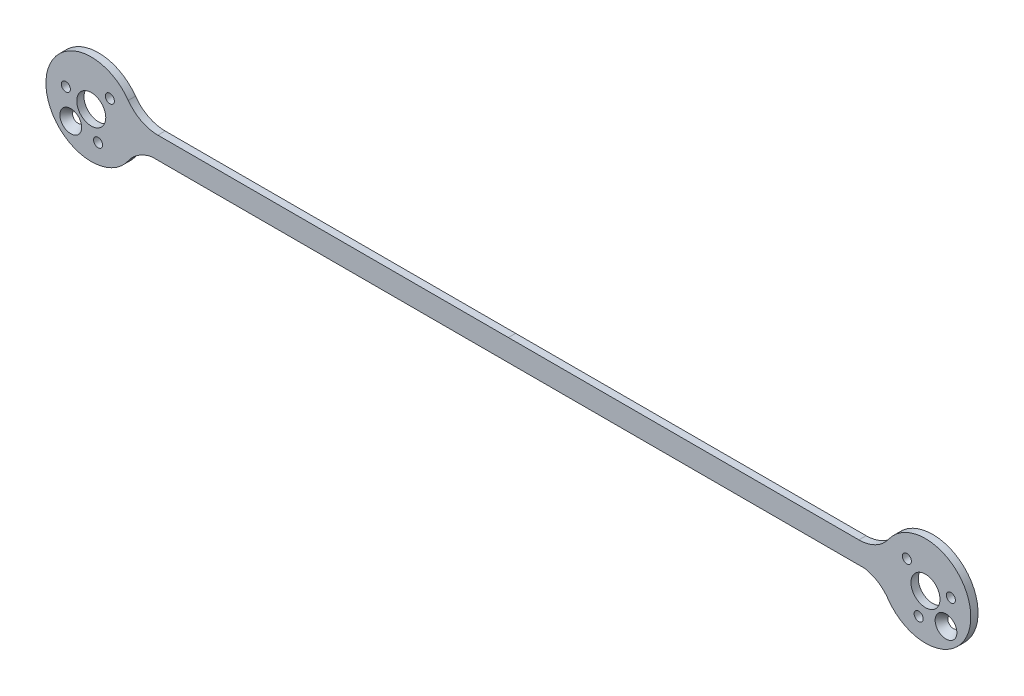
SolidWorks part; units mm, degrees
material "Thornel Mat VMA"
ref_plane "前视基准面" through (0, 0, 0) normal (0, 0, 1) x (1, 0, 0)
ref_plane "上视基准面" through (0, 0, 0) normal (0, 1, 0) x (1, 0, 0)
ref_plane "右视基准面" through (0, 0, 0) normal (1, 0, 0) x (0, 0, -1)
sketch "草图1" plane through (0, 0, 0) normal (0, 0, 1) x (1, 0, 0)
  line L0 (-99.1761, -2.9774) -> (-0.9213, -2.9774)
  line L1 (-0.9213, -2.9774) -> (97.3335, -2.9772)
  line L2 (95.7144, 3.0228) -> (-0.9213, 3.0226)
  line L3 (-0.9213, 3.0226) -> (-97.557, 3.0226)
  circle A0 centre (108.9522, 5.1492) radius 1.25
  arc A1 (-99.1761, -2.9774) -> (-105.6605, -7.1164) centre (-97.4519, -12.8277) ccw
  arc A2 (103.818, -7.1162) -> (97.3335, -2.9772) centre (95.6093, -12.8275) ccw
  arc A3 (103.818, -7.1162) -> (103.8763, 7.2449) centre (114.0786, 0.0228) ccw
  arc A4 (95.7144, 3.0228) -> (103.8763, 7.2449) centre (95.7144, 13.0228) ccw
  arc A5 (-105.7189, 7.2447) -> (-97.557, 3.0226) centre (-97.557, 13.0226) ccw
  arc A6 (-105.7189, 7.2447) -> (-105.6605, -7.1164) centre (-115.9212, 0.0225) ccw
  circle A7 centre (-114.0448, -6.9803) radius 1.25
  circle A8 centre (121.0817, 1.8991) radius 1.25
  circle A9 centre (-122.9242, 1.8991) radius 1.25
  circle A10 centre (-110.7948, 5.1492) radius 1.25
  circle A11 centre (114.0786, 0.0228) radius 4
  circle A12 centre (112.2023, -6.9803) radius 1.25
  circle A13 centre (119.7356, -5.6342) radius 3
  circle A14 centre (119.7356, -5.6342) radius 1.5
  circle A15 centre (-121.5781, -5.6342) radius 1.5
  circle A16 centre (-115.9212, 0.0225) radius 4
  circle A17 centre (-121.5781, -5.6342) radius 3
  dimension "D1" = 6
extrude "凸台-拉伸1" add sketch "草图1" along normal blind 2 contours A5 A6 A1 L0 L1 A2 A3 A4 L2 L3 A17 A16 A13 A12 A11 A10 A9 A8 A7 A0 | A17 A15 | A13 A14 region at (-0.9213, 0.1812, 0) region at (116.8204, -5.6342, 0) region at (-124.4933, -5.6342, 0)
chamfer "倒角1" distance 1.5 distance2 2 2 edges at (-120.0781, -5.6342, 2) (121.2356, -5.6342, 2) first distance on face at (-111.9212, 0.0225, 2)
